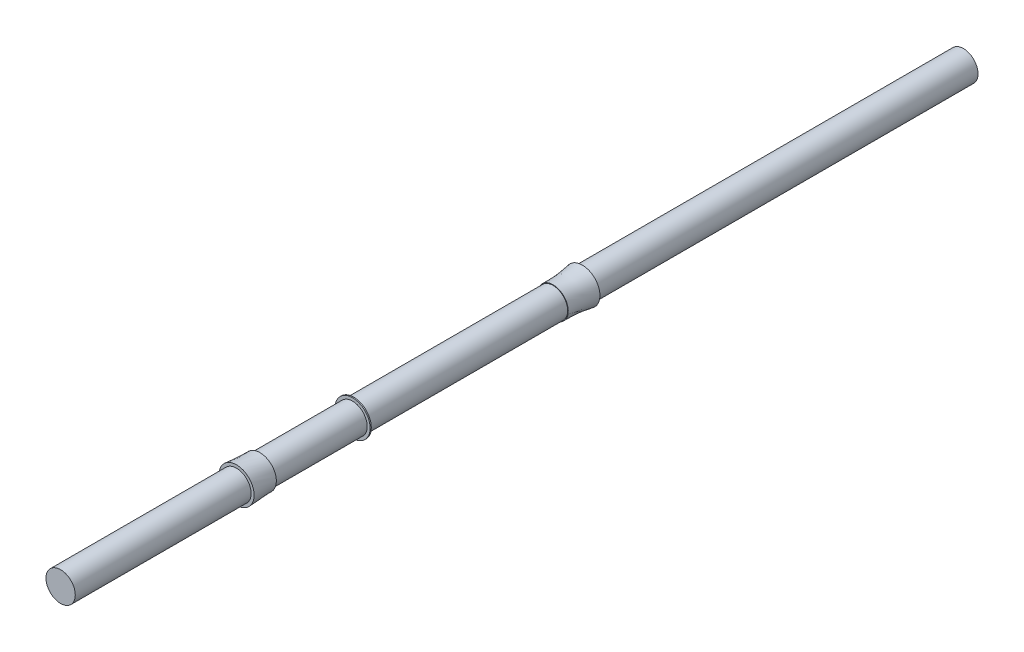
SolidWorks part; units mm, degrees
ref_plane "Front Plane" through (0, 0, 0) normal (0, 0, 1) x (1, 0, 0)
ref_plane "Top Plane" through (0, 0, 0) normal (0, 1, 0) x (1, 0, 0)
ref_plane "Right Plane" through (0, 0, 0) normal (1, 0, 0) x (0, 0, -1)
sketch "Sketch1" plane through (0, 0, 0) normal (0, 0, 1) x (1, 0, 0)
  circle A0 centre (0, 0) radius 12.5
extrude "Boss-Extrude1" add sketch "Sketch1" along normal blind 750
ref_plane "Plane1" through (0, 0, 500) normal (0, 0, 1) x (1, 0, 0)
sketch "Sketch2" plane through (0, 0, 500) normal (0, 0, 1) x (1, 0, 0)
  circle A0 centre (0, 0) radius 15
extrude "Boss-Extrude2" add sketch "Sketch2" along normal blind 1
ref_plane "Plane2" through (0, 0, 305) normal (0, 0, 1) x (1, 0, 0)
sketch "Sketch3" plane through (0, 0, 305) normal (0, 0, 1) x (1, 0, 0)
  circle A0 centre (0, 0) radius 15
ref_plane "Plane3" through (0, 0, 330) normal (0, 0, 1) x (1, 0, 0)
sketch "Sketch4" plane through (0, 0, 330) normal (0, 0, 1) x (1, 0, 0)
  circle A0 centre (0, 0) radius 13
loft "Loft1" add profiles "Sketch3", "Sketch4" connector at (9.8132, -11.3447, 305) connector at (12.7573, -2.5001, 330)
sketch "Sketch5" plane through (0, 0, 0) normal (0, 0, -1) x (-1, 0, 0)
  circle A0 centre (0, 0) radius 12.5
extrude "Boss-Extrude3" add sketch "Sketch5" along normal blind 20
ref_plane "Plane4" through (0, 0, 600) normal (0, 0, 1) x (1, 0, 0)
ref_plane "Plane5" through (0, 0, 580) normal (0, 0, 1) x (1, 0, 0)
sketch "Sketch6" plane through (0, 0, 600) normal (0, 0, 1) x (1, 0, 0)
  circle A0 centre (0, 0) radius 14.9981
sketch "Sketch7" plane through (0, 0, 580) normal (0, 0, 1) x (1, 0, 0)
  circle A0 centre (0, 0) radius 14
loft "Loft2" add profiles "Sketch6", "Sketch7" connector at (12.8613, -7.7156, 600) connector at (8.7397, -10.937, 580)
